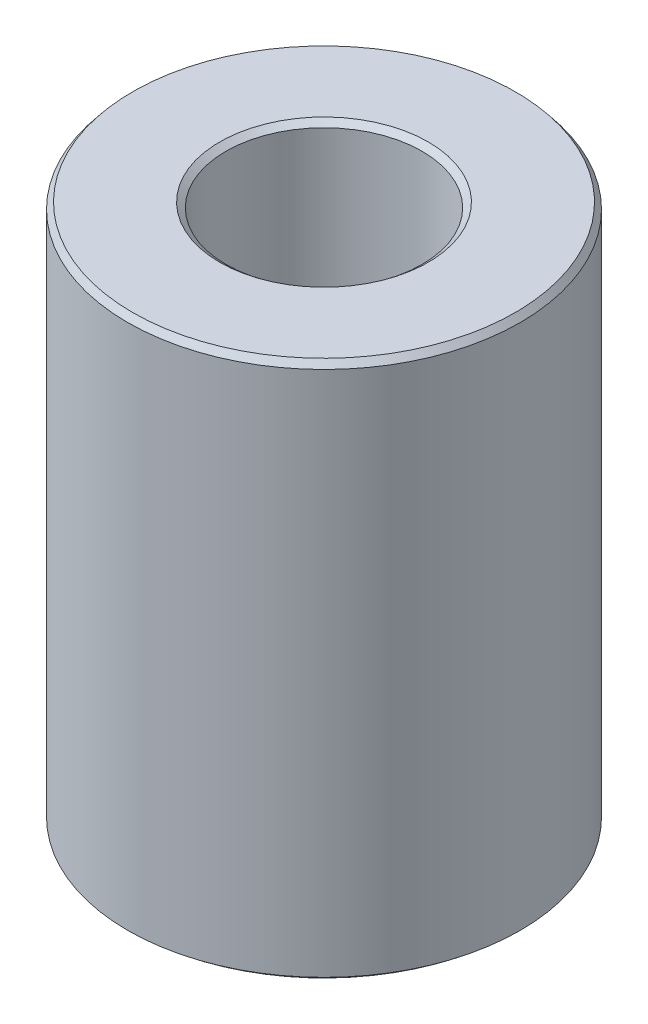
SolidWorks part; units mm, degrees
ref_plane "Front Plane" through (0, 0, 0) normal (0, 0, 1) x (1, 0, 0)
ref_plane "Top Plane" through (0, 0, 0) normal (0, 1, 0) x (1, 0, 0)
ref_plane "Right Plane" through (0, 0, 0) normal (1, 0, 0) x (0, 0, -1)
sketch "Sketch1" plane through (0, 0, 0) normal (0, 1, 0) x (1, 0, 0)
  circle A0 centre (0, 0) radius 35
  dimension "SLEEVE_OD" = 70
extrude "Boss-Extrude1" add sketch "Sketch1" along normal blind 95.8868
sketch "Sketch2" plane through (0, 0, 0) normal (0, 1, 0) x (1, 0, 0)
  circle A0 centre (0, 0) radius 17.4925
  dimension "BORE_D" = 34.9851
extrude "Cut-Extrude1" cut sketch "Sketch2" along normal through all
chamfer "Chamfer1" distance 1.1071 angle 38.548 4 edges at (0, 95.8868, 17.4925) (0, 0, 17.4925) (0, 0, 35) (0, 95.8868, 35) first distance on face at (0, 95.8868, 17.4925) first distance on face at (0, 0, 17.4925) first distance on face at (0, 95.8868, 35)
